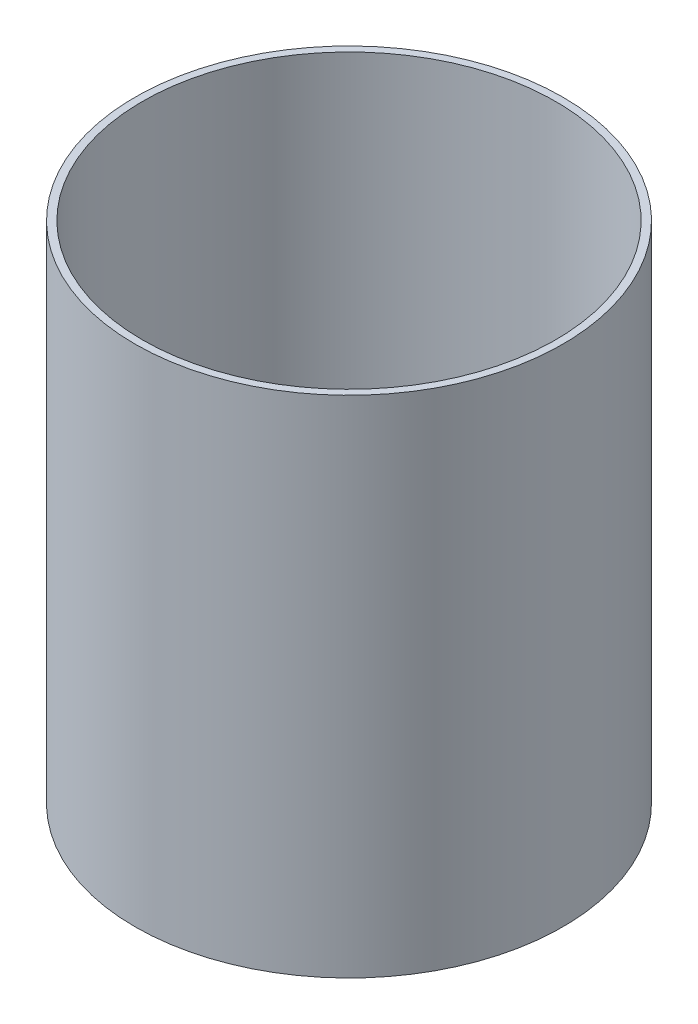
SolidWorks part; units mm, degrees
material "AISI 304"
ref_plane "Front" through (0, 0, 0) normal (0, 0, 1) x (1, 0, 0)
ref_plane "Top" through (0, 0, 0) normal (0, 1, 0) x (1, 0, 0)
ref_plane "Right" through (0, 0, 0) normal (1, 0, 0) x (0, 0, -1)
sketch "Sketch1" plane through (0, 0, 0) normal (0, 1, 0) x (1, 0, 0)
  circle A0 centre (0, 0) radius 109.5375
  circle A1 centre (0, 0) radius 105.7783
  dimension "D1" = 219.075
  dimension "D2" = 3.7592
extrude "Boss-Extrude1" add sketch "Sketch1" along normal mid plane 258.415
